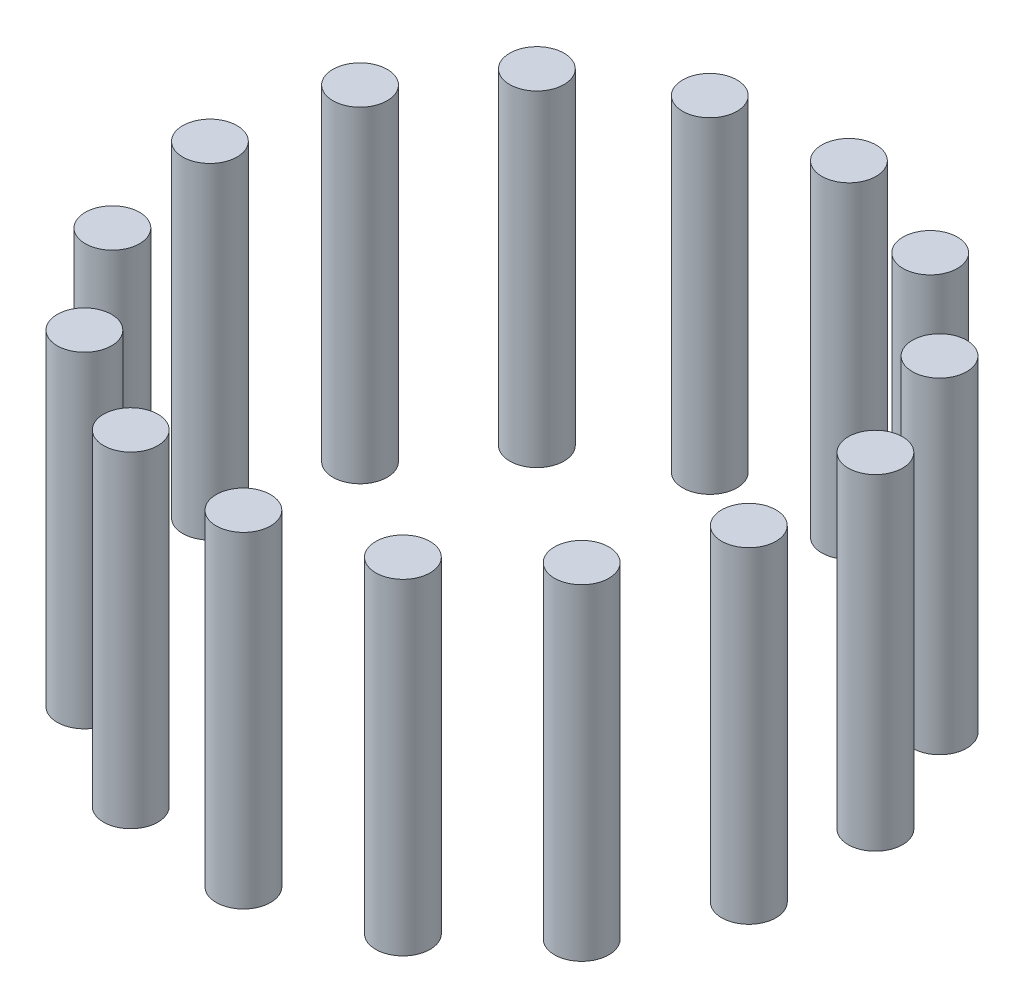
SolidWorks part; units mm, degrees
ref_plane "Front" through (0, 0, 0) normal (0, 0, 1) x (1, 0, 0)
ref_plane "Top" through (0, 0, 0) normal (0, 1, 0) x (1, 0, 0)
ref_plane "Right" through (0, 0, 0) normal (1, 0, 0) x (0, 0, -1)
sketch "Sketch1" plane through (0, 0, 0) normal (0, 1, 0) x (1, 0, 0)
  line L0 (0, 0) -> (27.3881, 5.8215) construction
  circle A0 centre (27.3881, 5.8215) radius 2.5
  circle A1 centre (27.3881, -5.8215) radius 2.5
  circle A2 centre (22.6525, -16.458) radius 2.5
  circle A3 centre (14, -24.2487) radius 2.5
  circle A4 centre (2.9268, -27.8466) radius 2.5
  circle A5 centre (-8.6525, -26.6296) radius 2.5
  circle A6 centre (-18.7357, -20.8081) radius 2.5
  circle A7 centre (-25.5793, -11.3886) radius 2.5
  circle A8 centre (-28, 0) radius 2.5
  circle A9 centre (-25.5793, 11.3886) radius 2.5
  circle A10 centre (-18.7357, 20.8081) radius 2.5
  circle A11 centre (-8.6525, 26.6296) radius 2.5
  circle A12 centre (2.9268, 27.8466) radius 2.5
  circle A13 centre (14, 24.2487) radius 2.5
  circle A14 centre (22.6525, 16.458) radius 2.5
  dimension "D3" = 5
  dimension "D1" = 12
  dimension "D2" = 28
  dimension "D4" = 15
extrude "Boss-Extrude1" add sketch "Sketch1" along normal blind 30
ref_axis "Axis1" through (0, -50, 0) along (0, 1, 0)
